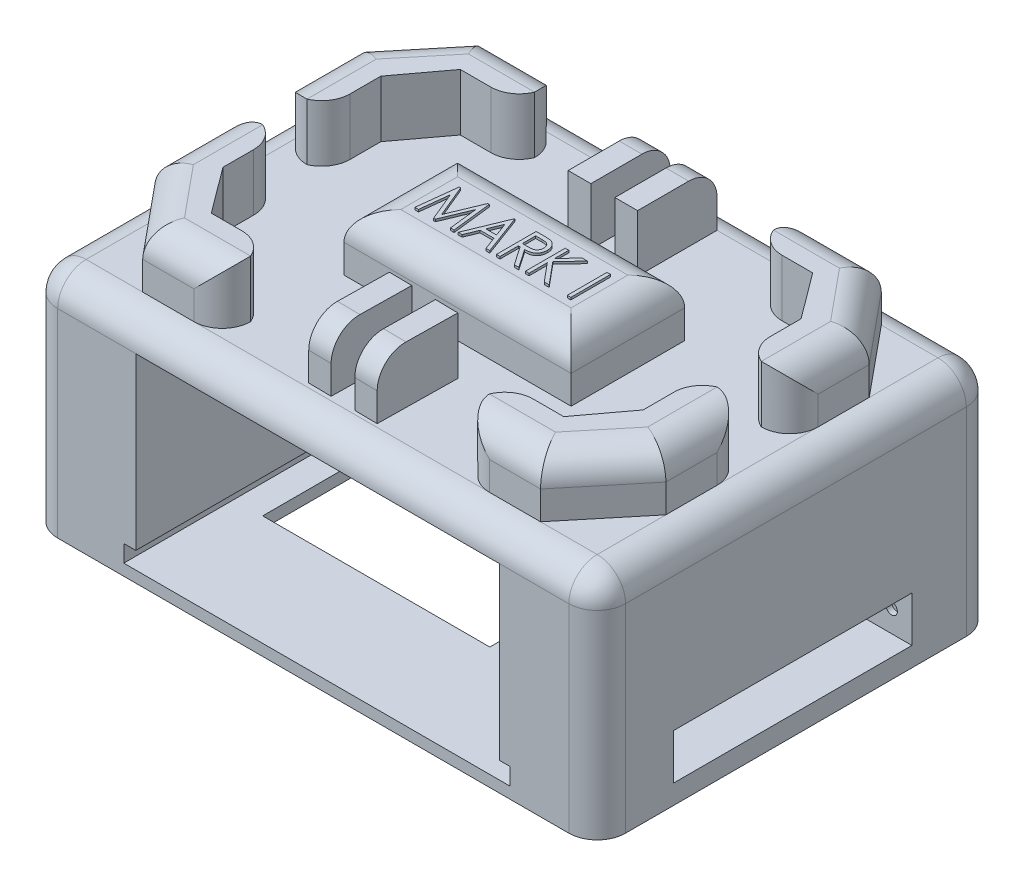
SolidWorks part; units mm, degrees
ref_plane "Front Plane" through (0, 0, 0) normal (0, 0, 1) x (1, 0, 0)
ref_plane "Top Plane" through (0, 0, 0) normal (0, 1, 0) x (1, 0, 0)
ref_plane "Right Plane" through (0, 0, 0) normal (1, 0, 0) x (0, 0, -1)
sketch "Sketch1" plane through (0, 0, 0) normal (0, 1, 0) x (1, 0, 0)
  line L1 (-23.6162, 13.5609) -> (26.3838, 13.5609)
  line L2 (-23.6162, 13.5609) -> (-23.6162, -21.4391)
  line L3 (-23.6162, -21.4391) -> (26.3838, -21.4391)
  line L4 (26.3838, 13.5609) -> (26.3838, -21.4391)
  dimension "D1" = 50
  dimension "D2" = 35
extrude "Boss-Extrude2" add sketch "Sketch1" along normal blind 20
sketch "Sketch3" plane through (0, 0, 21.4391) normal (0, 0, 1) x (1, 0, 0)
  line L0 (-23.6162, 0) -> (26.3838, 0) construction
  line L1 (18.703, 0) -> (-15.297, 0)
  line L2 (18.703, 0) -> (18.703, 1)
  line L3 (18.703, 1) -> (-15.297, 1)
  line L4 (-15.297, 0) -> (-15.297, 1)
  line L6 (18.703, 1) -> (-15.297, 1)
  line L7 (18.703, 1) -> (18.703, 2.5)
  line L8 (18.703, 2.5) -> (-15.297, 2.5)
  line L9 (-15.297, 1) -> (-15.297, 2.5)
  line L10 (-14.2369, 2.5) -> (17.7631, 2.5)
  line L11 (-14.2369, 2.5) -> (-14.2369, 17.5)
  line L12 (-14.2369, 17.5) -> (17.7631, 17.5)
  line L13 (17.7631, 2.5) -> (17.7631, 17.5)
  dimension "D1" = 34
  dimension "D2" = 1
  dimension "D3" = 34
  dimension "D4" = 1.5
  dimension "D5" = 32
  dimension "D6" = 15
extrude "Cut-Extrude1" cut sketch "Sketch3" against normal blind 22.5 contours L8 L13 L12 L11 | L9 L3 L7 L8
sketch "Sketch4" plane through (-23.6162, 0, 0) normal (-1, 0, 0) x (0, 0, 1)
  line L1 (-6.3367, 5.647) -> (14.6633, 5.647)
  line L2 (-6.3367, 5.647) -> (-6.3367, 1.647)
  line L3 (-6.3367, 1.647) -> (14.6633, 1.647)
  line L4 (14.6633, 5.647) -> (14.6633, 1.647)
  dimension "D1" = 21
  dimension "D2" = 4
extrude "Cut-Extrude2" cut sketch "Sketch4" against normal blind 4
sketch "Sketch5" plane through (0, 0, -6.3367) normal (0, 0, 1) x (1, 0, 0)
  circle A0 centre (-21.6223, 3.7617) radius 0.5
  dimension "D1" = 1
extrude "Cut-Extrude3" cut sketch "Sketch5" against normal blind 0.5 contours A0
sketch "Sketch6" plane through (0, 0, 14.6633) normal (0, 0, -1) x (-1, 0, 0)
  circle A0 centre (21.671, 3.6716) radius 0.5
  point P2 (21.671, 3.6716)
  dimension "D1" = 1
extrude "Cut-Extrude4" cut sketch "Sketch6" against normal blind 0.5
sketch "Sketch7" plane through (26.3838, 0, 0) normal (1, 0, 0) x (0, 0, -1)
  line L1 (-14.7281, 5.7109) -> (6.2719, 5.7109)
  line L2 (-14.7281, 5.7109) -> (-14.7281, 1.7109)
  line L3 (-14.7281, 1.7109) -> (6.2719, 1.7109)
  line L4 (6.2719, 5.7109) -> (6.2719, 1.7109)
  dimension "D1" = 21
  dimension "D2" = 4
extrude "Cut-Extrude5" cut sketch "Sketch7" against normal blind 4 contours L2 L1 L4 L3
sketch "Sketch8" plane through (0, 0, 14.7281) normal (0, 0, -1) x (-1, 0, 0)
  circle A0 centre (-24.4029, 3.6889) radius 0.5
  point P2 (0, 0)
  point P3 (-24.4746, 3.6971)
  point P4 (0, 0)
  point P5 (-24.1941, 3.7074)
  point P6 (0, 0)
  dimension "D1" = 1
extrude "Cut-Extrude6" cut sketch "Sketch8" against normal blind 0.5 contours A0
sketch "Sketch9" plane through (0, 0, -6.2719) normal (0, 0, 1) x (1, 0, 0)
  circle A0 centre (24.6008, 3.643) radius 0.5
  point P2 (0, 0)
  point P3 (24.6008, 3.643)
  dimension "D1" = 1
extrude "Cut-Extrude7" cut sketch "Sketch9" against normal blind 0.5
fillet "Fillet2" radius 2.5 8 edges at (1.3838, 20, 21.4391) (-23.6162, 10, 21.4391) (-23.6162, 20, 3.9391) (-23.6162, 10, -13.5609) (26.3838, 10, 21.4391) (26.3838, 10, -13.5609) (26.3838, 20, 3.9391) (1.3838, 20, -13.5609)
sketch "Sketch11" plane through (0, 20, 0) normal (0, 1, 0) x (1, 0, 0)
  line L0 (-21.1162, 11.0609) -> (-21.1162, -18.9391) construction
  line L1 (-21.1162, -1.9871) -> (-21.1162, 5.0129)
  line L2 (-21.1162, 5.0129) -> (-16.1311, 11.0609)
  line L3 (23.8838, 11.0609) -> (-21.1162, 11.0609) construction
  line L4 (-16.1311, 11.0609) -> (-9.1311, 11.0609)
  line L5 (-9.1311, 11.0609) -> (-9.1311, 7.0205)
  line L6 (-9.1311, 7.0205) -> (-14.1311, 7.0205)
  line L7 (-14.1311, 7.0205) -> (-17.1162, 3.0129)
  line L8 (-17.1162, 3.0129) -> (-17.1162, -1.9871)
  line L9 (-17.1162, -1.9871) -> (-21.1162, -1.9871)
  line L10 (-21.1162, -6.5524) -> (-21.1162, -3.9391)
  line L11 (-21.1162, -3.9391) -> (23.8838, -3.9391)
  line L12 (-17.1162, -10.8911) -> (-17.1162, -5.8911)
  line L13 (-14.1311, -14.8988) -> (-17.1162, -10.8911)
  line L14 (-9.1311, -14.8988) -> (-14.1311, -14.8988)
  line L15 (-9.1311, -18.9391) -> (-9.1311, -14.8988)
  line L16 (-16.1311, -18.9391) -> (-9.1311, -18.9391)
  line L17 (-21.1162, -12.8911) -> (-16.1311, -18.9391)
  line L18 (-21.1162, -5.8911) -> (-21.1162, -12.8911)
  line L19 (-17.1162, -5.8911) -> (-21.1162, -5.8911)
  line L21 (19.8838, 3.0129) -> (19.8838, -1.9871)
  line L22 (16.8986, 7.0205) -> (19.8838, 3.0129)
  line L23 (11.8986, 7.0205) -> (16.8986, 7.0205)
  line L24 (11.8986, 11.0609) -> (11.8986, 7.0205)
  line L25 (18.8986, 11.0609) -> (11.8986, 11.0609)
  line L26 (23.8838, 5.0129) -> (18.8986, 11.0609)
  line L27 (23.8838, -1.9871) -> (23.8838, 5.0129)
  line L28 (19.8838, -1.9871) -> (23.8838, -1.9871)
  line L29 (23.8838, -18.9391) -> (23.8838, 11.0609) construction
  line L30 (16.8986, -14.8988) -> (19.8838, -10.8911)
  line L31 (11.8986, -14.8988) -> (16.8986, -14.8988)
  line L32 (11.8986, -18.9391) -> (11.8986, -14.8988)
  line L33 (18.8986, -18.9391) -> (11.8986, -18.9391)
  line L34 (23.8838, -12.8911) -> (18.8986, -18.9391)
  line L35 (23.8838, -5.8911) -> (23.8838, -12.8911)
  line L36 (19.8838, -5.8911) -> (23.8838, -5.8911)
  line L37 (19.8838, -10.8911) -> (19.8838, -5.8911)
  line M29 (-21.1162, 11.0609) -> (-21.1162, -18.9391)
  line M30 (-21.1162, -18.9391) -> (23.8838, -18.9391)
  line M31 (23.8838, -18.9391) -> (23.8838, 11.0609)
  line M32 (23.8838, 11.0609) -> (-21.1162, 11.0609)
  dimension "D1" = 7
  dimension "D2" = 7
  dimension "D3" = 4
  dimension "D4" = 4.0403
  dimension "D5" = 5
  dimension "D6" = 5
extrude "Boss-Extrude4" add sketch "Sketch11" along normal blind 5 contours L9 L8 L7 L6 L5 L2 M32 M29 | L12 L19 L10 L17 L15 L14 L13 M29 M30 | L37 L30 L31 L32 L34 L36 M30 M31 | L21 L28 L26 L24 L23 L22 M31 M32
fillet "Fillet4" radius 2.5 5 edges at (-9.1311, 22.5, 18.9391) (-21.1162, 22.5, 5.8911) (-12.6311, 25, 18.9391) (-18.6237, 25, 15.9151) (-21.1162, 25, 9.3911)
fillet "Fillet5" radius 2.5 10 edges at (11.8986, 22.5, -11.0609) (15.3986, 25, -11.0609) (21.3912, 25, -8.0369) (23.8838, 25, -1.5129) (23.8838, 22.5, 1.9871) (23.8838, 22.5, 5.8911) (11.8986, 22.5, 18.9391) (23.8838, 25, 9.3911) (21.3912, 25, 15.9151) (15.3986, 25, 18.9391)
fillet "Fillet6" radius 2.5 5 edges at (-9.1311, 22.5, -11.0609) (-21.1162, 22.5, 1.9871) (-12.6311, 25, -11.0609) (-18.6237, 25, -8.0369) (-21.1162, 25, -1.5129)
sketch "Sketch12" plane through (0, 20, 0) normal (0, 1, 0) x (1, 0, 0)
  line L0 (1.3838, 11.0609) -> (1.3838, -18.9391)
  line L1 (14.3986, 11.0609) -> (-11.6311, 11.0609) construction
  line L2 (-11.6311, -18.9391) -> (14.3986, -18.9391) construction
  line L3 (2.4419, 4.0609) -> (4.4419, 4.0609)
  line L4 (0.3256, 11.0609) -> (-1.6744, 11.0609)
  line L5 (0.3256, 11.0609) -> (0.3256, 4.0609)
  line L6 (0.3256, 4.0609) -> (-1.6744, 4.0609)
  line L7 (-1.6744, 11.0609) -> (-1.6744, 4.0609)
  line L8 (4.4419, 11.0609) -> (4.4419, 4.0609)
  line L9 (2.4419, 11.0609) -> (4.4419, 11.0609)
  line L10 (2.4419, 11.0609) -> (2.4419, 4.0609)
  line L11 (-21.1162, -3.6055) -> (23.8838, -3.9391)
  line L12 (-21.1162, 0.5129) -> (-21.1162, -8.3911) construction
  line L13 (23.8838, -8.3911) -> (23.8838, 0.5129) construction
  line L14 (2.2219, -18.6196) -> (2.3257, -11.6203)
  line L15 (2.2219, -18.6196) -> (4.2216, -18.6492)
  line L16 (4.2216, -18.6492) -> (4.3254, -11.65)
  line L17 (2.3257, -11.6203) -> (4.3254, -11.65)
  line L18 (0.2096, -11.5889) -> (-1.7902, -11.5593)
  line L19 (-1.894, -18.5585) -> (-1.7902, -11.5593)
  line L20 (0.1058, -18.5882) -> (-1.894, -18.5585)
  line L21 (0.1058, -18.5882) -> (0.2096, -11.5889)
  line M23 (14.3986, 11.0609) -> (-11.6311, 11.0609)
  dimension "D1" = 2
  dimension "D2" = 7
sketch "Sketch15" plane through (0, 20, 0) normal (0, 1, 0) x (1, 0, 0)
extrude "Boss-Extrude5" add sketch "Sketch12" along normal blind 5 contours L7 L6 L5 M23 | L10 L3 L8 M23 | L17 L14 L15 L16 | L20 L21 L18 L19
sketch "Sketch16" plane through (0, 20, 0) normal (0, 1, 0) x (1, 0, 0)
  line L1 (-8.5698, 1.2192) -> (11.4302, 1.2192)
  line L2 (-8.5698, 1.2192) -> (-8.5698, -8.7808)
  line L3 (-8.5698, -8.7808) -> (11.4302, -8.7808)
  line L4 (11.4302, 1.2192) -> (11.4302, -8.7808)
  dimension "D1" = 20
  dimension "D2" = 10
extrude "Boss-Extrude6" add sketch "Sketch16" along normal blind 5 contours L2 L1 L4 L3
fillet "Fillet7" radius 2.5 4 edges at (1.4302, 25, 8.7808) (11.4302, 25, 3.7808) (1.4302, 25, -1.2192) (-8.5698, 25, 3.7808)
sketch "Sketch19" plane through (0, 0, -13.5609) normal (0, 0, -1) x (-1, 0, 0)
  text T0 "Stress Controller\r\nMark I"
extrude "Boss-Extrude7" add sketch "Sketch19" along normal blind 0.2
sketch "Sketch20" plane through (0, 25, 0) normal (0, 1, 0) x (1, 0, 0)
  text T0 "MARK I" font "Century Gothic" height 3.5
extrude "Boss-Extrude8" add sketch "Sketch20" along normal blind 0.2
sketch "Sketch21" plane through (0, 0, 0) normal (0, -1, 0) x (1, 0, 0)
  line L1 (-12.7876, 11.7201) -> (7.2124, 11.7201)
  line L2 (-12.7876, 11.7201) -> (-12.7876, 1.7201)
  line L3 (-12.7876, 1.7201) -> (7.2124, 1.7201)
  line L4 (7.2124, 11.7201) -> (7.2124, 1.7201)
  point P4 (7.0796, 12.8111)
  dimension "D1" = 20
  dimension "D2" = 10
sketch "Sketch25" plane through (0, 0, 0) normal (0, -1, 0) x (1, 0, 0)
extrude "Cut-Extrude10" cut sketch "Sketch21" against normal blind 2
fillet "Fillet8" radius 2.5 4 edges at (-9.1311, 22.5, 14.8988) (-17.1162, 22.5, 5.8911) (-17.1162, 22.5, 1.9871) (-9.1311, 22.5, -7.0205)
fillet "Fillet9" radius 2.5 4 edges at (11.8986, 22.5, 14.8988) (19.8838, 22.5, 5.8911) (19.8838, 22.5, 1.9871) (11.8986, 22.5, -7.0205)
fillet "Fillet10" radius 2.5 4 edges at (3.2218, 25, 18.6344) (-0.8941, 25, 18.5734) (-0.6744, 25, -11.0609) (3.4419, 25, -11.0609)
